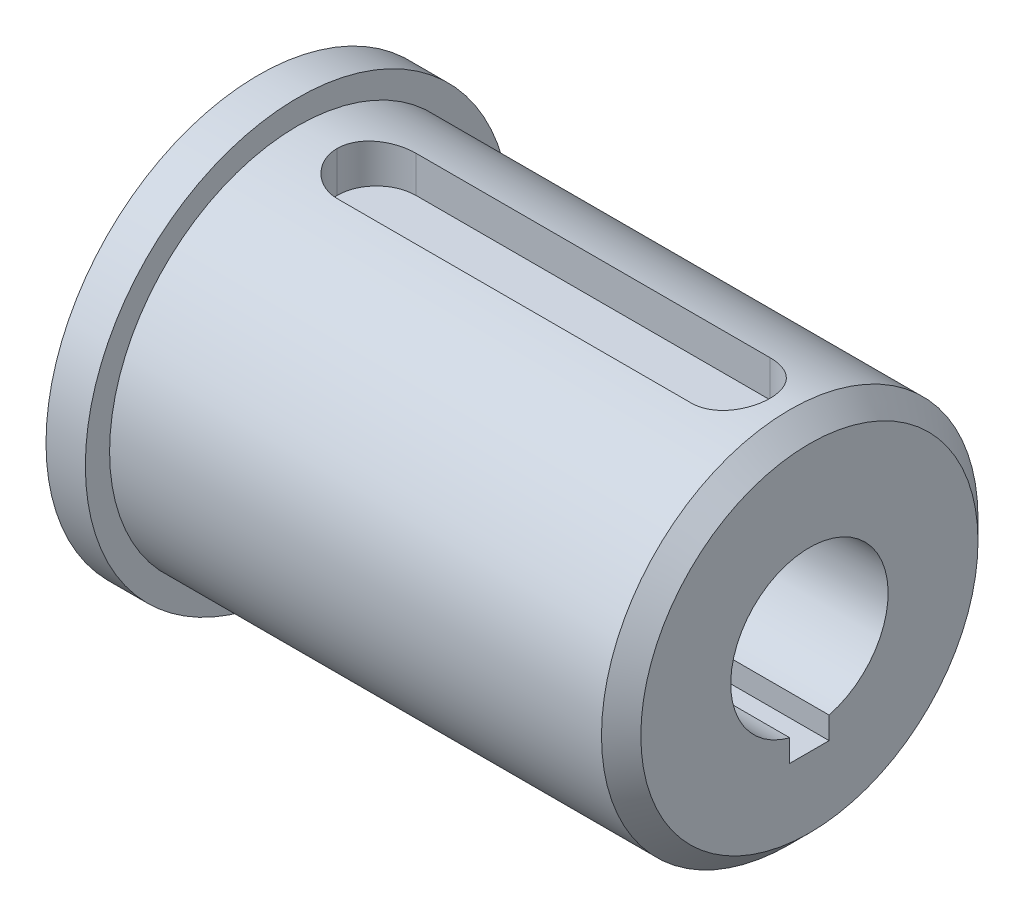
SolidWorks part; units mm, degrees
material "Delrin 2700 NC010, Low Viscosity Acetal Copolymer (SS)"
ref_plane "Front Plane" through (0, 0, 0) normal (0, 0, 1) x (1, 0, 0)
ref_plane "Top Plane" through (0, 0, 0) normal (0, 1, 0) x (1, 0, 0)
ref_plane "Right Plane" through (0, 0, 0) normal (1, 0, 0) x (0, 0, -1)
sketch "Sketch1" plane through (0, 0, 0) normal (1, 0, 0) x (0, 0, -1)
  circle A0 centre (0, 0) radius 6.35
  circle A1 centre (0, 0) radius 15.1892
extrude "Boss-Extrude1" add sketch "Sketch1" along normal blind 41.275
sketch "Sketch2" plane through (41.275, 0, 0) normal (1, 0, 0) x (0, 0, -1)
  line L0 (0, 0) -> (0, 6.35) construction
  line L1 (0, 6.35) -> (0, 15.0812) construction
  line L2 (0, 6.35) -> (0, -4.7625) construction
  line L3 (-1.5875, -7.9375) -> (1.5875, -7.9375)
  line L4 (-1.5875, -7.9375) -> (-1.5875, -4.7625)
  line L5 (-1.5875, -4.7625) -> (1.5875, -4.7625)
  line L6 (1.5875, -7.9375) -> (1.5875, -4.7625)
  line L7 (3.175, 18.2562) -> (-3.175, 18.2562)
  line L8 (3.175, 18.2562) -> (3.175, 11.9062)
  line L9 (3.175, 11.9062) -> (-3.175, 11.9062)
  line L10 (-3.175, 18.2562) -> (-3.175, 11.9062)
  line L11 (0, 15.0812) -> (0, 11.9062) construction
  circle A0 centre (0, 0) radius 6.35 construction
  dimension "D1" = 6.35
  dimension "D2" = 15.0812
  dimension "D3" = 3.175
  dimension "D4" = 7.9375
  dimension "D5" = 3.175
  dimension "D6" = 3.175
extrude "Cut-Extrude1" cut sketch "Sketch2" against normal through all
sketch "Sketch3" plane through (0, 0, 0) normal (-1, 0, 0) x (0, 0, 1)
  line L5 (-1.5875, -7.9375) -> (1.5875, -7.9375)
  line L6 (-1.5875, -7.9375) -> (-1.5875, -6.1484)
  line L7 (-1.5875, -6.1484) -> (1.5875, -6.1484)
  line L8 (1.5875, -7.9375) -> (1.5875, -6.1484)
  circle A0 centre (0, 0) radius 17.145
  circle A1 centre (0, 0) radius 6.35
  arc M1 (-1.5875, -6.1484) -> (1.5875, -6.1484) centre (0, 0) cw
  line M2 (1.5875, -6.1484) -> (1.5875, -7.9375)
  line M3 (1.5875, -7.9375) -> (-1.5875, -7.9375)
  line M4 (-1.5875, -7.9375) -> (-1.5875, -6.1484)
  line M5 (3.175, 11.9062) -> (-3.175, 11.9062)
  line M6 (-3.175, 11.9062) -> (-3.175, 14.8537)
  arc M7 (-3.175, 14.8537) -> (3.175, 14.8537) centre (0, 0) ccw
  line M8 (3.175, 14.8537) -> (3.175, 11.9062)
extrude "Boss-Extrude2" add sketch "Sketch3" along normal blind 3.175 contours A0 M7 | M8 M5 M6 M7 M4 M1 M2 M3 region at (0, 0, -16.6601) region at (0, 13.38, 3.6022)
sketch "Sketch4" plane through (0, 0, 0) normal (1, 0, 0) x (0, 0, -1)
  line L2 (-3.175, 14.8537) -> (-3.175, 11.9062)
  line L3 (-3.175, 11.9062) -> (3.175, 11.9062)
  line L4 (3.175, 14.8277) -> (3.175, 11.9062)
  circle A0 centre (0, 0) radius 15.1892
  arc A1 (-3.175, 14.8537) -> (3.175, 14.8537) centre (0, 0) ccw construction
  line M2 (3.175, 11.9062) -> (3.175, 14.8537)
  line M4 (-3.175, 14.8537) -> (-3.175, 11.9062)
  line M5 (-3.175, 11.9062) -> (3.175, 11.9062)
extrude "Boss-Extrude3" add sketch "Sketch4" along normal blind 3.175 contours A0 M2 M4 M5 region at (0, 13.4936, 0)
sketch "Sketch5" plane through (41.275, 0, 0) normal (1, 0, 0) x (0, 0, -1)
  circle A0 centre (0, 0) radius 15.1892
  circle A1 centre (0, 0) radius 10.9679
  arc A2 (-3.175, 14.8537) -> (3.175, 14.8537) centre (0, 0) ccw construction
extrude "Boss-Extrude4" add sketch "Sketch5" against normal blind 3.175
fillet "Fillet1" radius 3.175 4 edges at (3.175, 13.38, -3.175) (3.175, 13.38, 3.175) (38.1, 13.38, 3.175) (38.1, 13.38, -3.175)
chamfer "Chamfer1" distance 1.5875 angle 45 1 edges at (41.275, 0, -15.1892)
